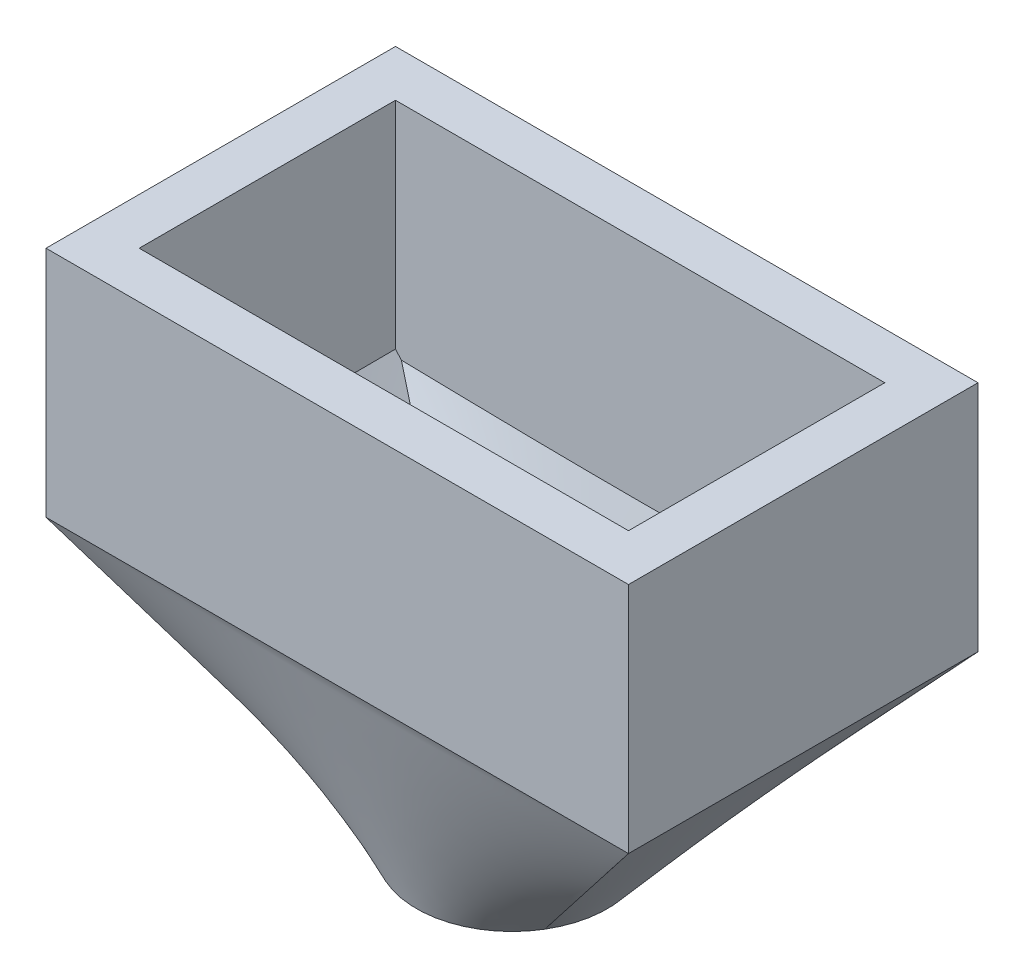
SolidWorks part; units mm, degrees
ref_plane "Plan de face" through (0, 0, 0) normal (0, 0, 1) x (1, 0, 0)
ref_plane "Plan de dessus" through (0, 0, 0) normal (0, 1, 0) x (1, 0, 0)
ref_plane "Plan de droite" through (0, 0, 0) normal (1, 0, 0) x (0, 0, -1)
sketch "Esquisse2" plane through (0, 0, 0) normal (0, 1, 0) x (1, 0, 0)
  line L1 (-15.32, 5.179) -> (9.68, 5.179)
  line L2 (-15.32, 5.179) -> (-15.32, -9.821)
  line L3 (-15.32, -9.821) -> (9.68, -9.821)
  line L4 (9.68, 5.179) -> (9.68, -9.821)
  dimension "D1" = 25
  dimension "D2" = 15
extrude "Boss.-Extru.1" add sketch "Esquisse2" along normal blind 10
ref_plane "Plan1" through (0, -10, 0) normal (0, -1, 0) x (-1, 0, 0)
sketch "Esquisse3" plane through (0, -10, 0) normal (0, -1, 0) x (-1, 0, 0)
  line L0 (-9.68, 5.179) -> (15.32, -9.821) construction
  line L1 (-9.68, -9.821) -> (15.32, 5.179) construction
  circle A0 centre (2.82, -2.321) radius 4.1
  point P10 (2.82, -2.321)
  dimension "D1" = 8.2
sketch "Esquisse4" plane through (0, 0, 0) normal (0, -1, 0) x (1, 0, 0)
  line L4 (-15.32, 9.821) -> (-15.32, -5.179)
  line L5 (-15.32, -5.179) -> (9.68, -5.179)
  line L6 (9.68, -5.179) -> (9.68, 9.821)
  line L7 (9.68, 9.821) -> (-15.32, 9.821)
  line L8 (-15.32, 9.821) -> (-15.32, -5.179)
  line L9 (-15.32, -5.179) -> (9.68, -5.179)
  line L10 (9.68, -5.179) -> (9.68, 9.821)
  line L11 (9.68, 9.821) -> (-15.32, 9.821)
  dimension "D1" = 0
loft "Lissage1" add profiles "Esquisse4", "Esquisse3" connector at (-15.32, 0, 9.821) connector at (-3.9068, -10, 6.2744)
shell "Coque1" thickness 2 removed face at (-2.82, 10, 2.321)
sketch "Esquisse5" plane through (0, -10, 0) normal (0, -1, 0) x (1, 0, 0)
  circle A0 centre (-2.82, 2.321) radius 4.1
extrude "Enlèv. mat.-Extru.1" cut sketch "Esquisse5" against normal blind 8
